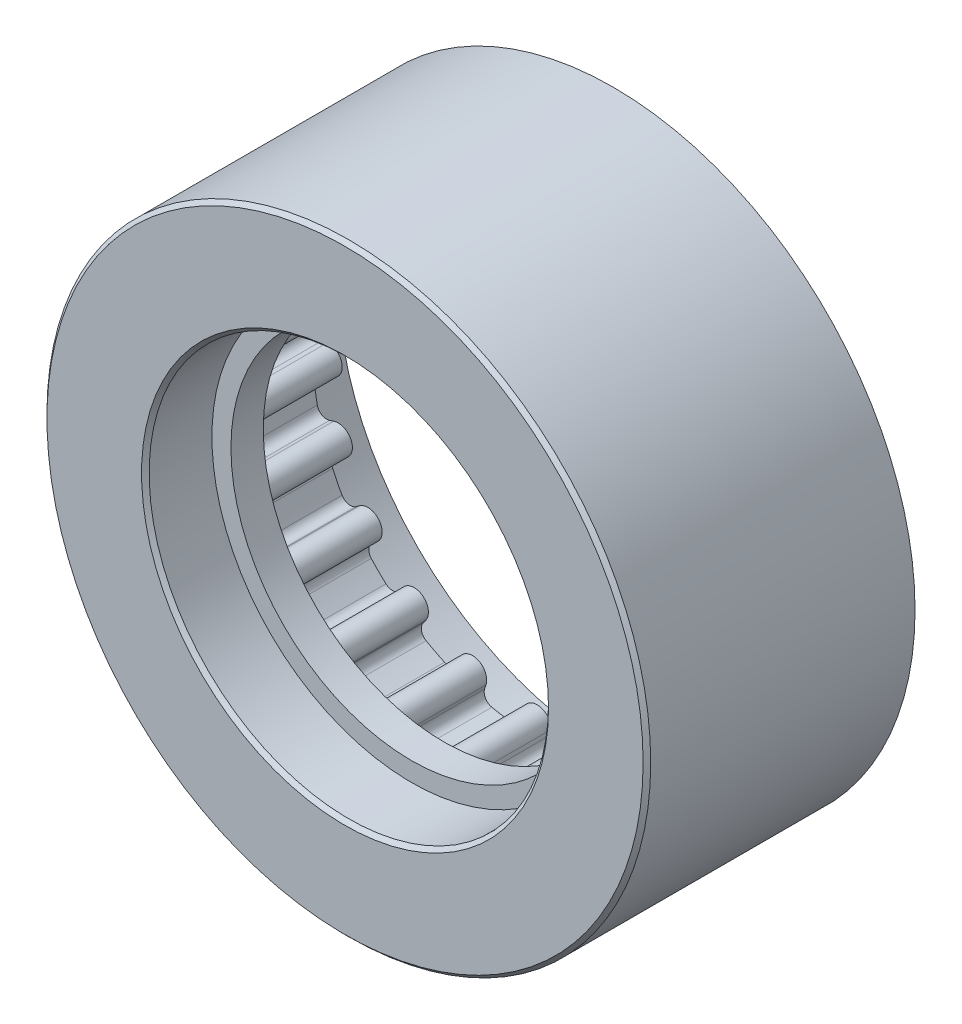
SolidWorks part; units mm, degrees
ref_plane "Ebene vorne" through (0, 0, 0) normal (0, 0, 1) x (1, 0, 0)
ref_plane "Ebene oben" through (0, 0, 0) normal (0, 1, 0) x (1, 0, 0)
ref_plane "Ebene rechts" through (0, 0, 0) normal (1, 0, 0) x (0, 0, -1)
ref_plane "Ebene1" through (0, 0, 0) normal (0, -1, 0) x (1, 0, 0)
sketch "Skizze1" plane through (0, 0, 0) normal (0, -1, 0) x (1, 0, 0)
  line L0 (31.75, 10.8) -> (0, 10.8)
  line L1 (0, 10.8) -> (0, -7)
  line L2 (0, -7) -> (31.75, -7)
  line L3 (31.75, -7) -> (31.75, 10.8)
  line L4 (0, 10.8) -> (0, -7) construction
revolve "Rotation1" add sketch "Skizze1" angle 360 about L4 reverse direction yes
sketch "Skizze2" plane through (0, 0, 10.8) normal (0, 0, 1) x (1, 0, 0)
  line L0 (-8.225, 20.4597) -> (-8.7046, 21.936)
  line L1 (-12.6302, 19.9359) -> (-11.7178, 18.6801)
  line L2 (-14.1448, 16.9167) -> (-15.0572, 18.1725)
  line L3 (-18.1725, 15.0572) -> (-16.9167, 14.1448)
  line L4 (-18.6801, 11.7178) -> (-19.9359, 12.6302)
  line L5 (-21.936, 8.7046) -> (-20.4597, 8.225)
  line L6 (-21.3868, 5.3718) -> (-22.8631, 5.8515)
  line L7 (-23.5523, 1.5) -> (-22, 1.5)
  line L8 (-22, -1.5) -> (-23.5523, -1.5)
  line L9 (-22.8631, -5.8515) -> (-21.3868, -5.3718)
  line L10 (-20.4597, -8.225) -> (-21.936, -8.7046)
  line L11 (-19.9359, -12.6302) -> (-18.6801, -11.7178)
  line L12 (-16.9167, -14.1448) -> (-18.1725, -15.0572)
  line L13 (-15.0572, -18.1725) -> (-14.1448, -16.9167)
  line L14 (-11.7178, -18.6801) -> (-12.6302, -19.9359)
  line L15 (-8.7046, -21.936) -> (-8.225, -20.4597)
  line L16 (-5.3718, -21.3868) -> (-5.8515, -22.8631)
  line L17 (-1.5, -23.5523) -> (-1.5, -22)
  line L18 (1.5, -22) -> (1.5, -23.5523)
  line L19 (5.8515, -22.8631) -> (5.3718, -21.3868)
  line L20 (8.225, -20.4597) -> (8.7046, -21.936)
  line L21 (12.6302, -19.9359) -> (11.7178, -18.6801)
  line L22 (14.1448, -16.9167) -> (15.0572, -18.1725)
  line L23 (18.1725, -15.0572) -> (16.9167, -14.1448)
  line L24 (18.6801, -11.7178) -> (19.9359, -12.6302)
  line L25 (21.936, -8.7046) -> (20.4597, -8.225)
  line L26 (21.3868, -5.3718) -> (22.8631, -5.8515)
  line L27 (23.5523, -1.5) -> (22, -1.5)
  line L28 (22, 1.5) -> (23.5523, 1.5)
  line L29 (22.8631, 5.8515) -> (21.3868, 5.3718)
  line L30 (20.4597, 8.225) -> (21.936, 8.7046)
  line L31 (19.9359, 12.6302) -> (18.6801, 11.7178)
  line L32 (16.9167, 14.1448) -> (18.1725, 15.0572)
  line L33 (15.0572, 18.1725) -> (14.1448, 16.9167)
  line L34 (11.7178, 18.6801) -> (12.6302, 19.9359)
  line L35 (8.7046, 21.936) -> (8.225, 20.4597)
  line L36 (5.3718, 21.3868) -> (5.8515, 22.8631)
  line L37 (1.5, 23.5523) -> (1.5, 22)
  line L38 (-1.5, 22) -> (-1.5, 23.5523)
  line L39 (-5.8515, 22.8631) -> (-5.3718, 21.3868)
  arc A0 (-8.7046, 21.936) -> (-12.6302, 19.9359) centre (0, 0) ccw
  arc A1 (-11.7178, 18.6801) -> (-14.1448, 16.9167) centre (-12.9313, 17.7984) cw
  arc A2 (-15.0572, 18.1725) -> (-18.1725, 15.0572) centre (0, 0) ccw
  arc A3 (-16.9167, 14.1448) -> (-18.6801, 11.7178) centre (-17.7984, 12.9313) cw
  arc A4 (-19.9359, 12.6302) -> (-21.936, 8.7046) centre (0, 0) ccw
  arc A5 (-20.4597, 8.225) -> (-21.3868, 5.3718) centre (-20.9232, 6.7984) cw
  arc A6 (-22.8631, 5.8515) -> (-23.5523, 1.5) centre (0, 0) ccw
  arc A7 (-22, 1.5) -> (-22, -1.5) centre (-22, 0) cw
  arc A8 (-23.5523, -1.5) -> (-22.8631, -5.8515) centre (0, 0) ccw
  arc A9 (-21.3868, -5.3718) -> (-20.4597, -8.225) centre (-20.9232, -6.7984) cw
  arc A10 (-21.936, -8.7046) -> (-19.9359, -12.6302) centre (0, 0) ccw
  arc A11 (-18.6801, -11.7178) -> (-16.9167, -14.1448) centre (-17.7984, -12.9313) cw
  arc A12 (-18.1725, -15.0572) -> (-15.0572, -18.1725) centre (0, 0) ccw
  arc A13 (-14.1448, -16.9167) -> (-11.7178, -18.6801) centre (-12.9313, -17.7984) cw
  arc A14 (-12.6302, -19.9359) -> (-8.7046, -21.936) centre (0, 0) ccw
  arc A15 (-8.225, -20.4597) -> (-5.3718, -21.3868) centre (-6.7984, -20.9232) cw
  arc A16 (-5.8515, -22.8631) -> (-1.5, -23.5523) centre (0, 0) ccw
  arc A17 (-1.5, -22) -> (1.5, -22) centre (0, -22) cw
  arc A18 (1.5, -23.5523) -> (5.8515, -22.8631) centre (0, 0) ccw
  arc A19 (5.3718, -21.3868) -> (8.225, -20.4597) centre (6.7984, -20.9232) cw
  arc A20 (8.7046, -21.936) -> (12.6302, -19.9359) centre (0, 0) ccw
  arc A21 (11.7178, -18.6801) -> (14.1448, -16.9167) centre (12.9313, -17.7984) cw
  arc A22 (15.0572, -18.1725) -> (18.1725, -15.0572) centre (0, 0) ccw
  arc A23 (16.9167, -14.1448) -> (18.6801, -11.7178) centre (17.7984, -12.9313) cw
  arc A24 (19.9359, -12.6302) -> (21.936, -8.7046) centre (0, 0) ccw
  arc A25 (20.4597, -8.225) -> (21.3868, -5.3718) centre (20.9232, -6.7984) cw
  arc A26 (22.8631, -5.8515) -> (23.5523, -1.5) centre (0, 0) ccw
  arc A27 (22, -1.5) -> (22, 1.5) centre (22, 0) cw
  arc A28 (23.5523, 1.5) -> (22.8631, 5.8515) centre (0, 0) ccw
  arc A29 (21.3868, 5.3718) -> (20.4597, 8.225) centre (20.9232, 6.7984) cw
  arc A30 (21.936, 8.7046) -> (19.9359, 12.6302) centre (0, 0) ccw
  arc A31 (18.6801, 11.7178) -> (16.9167, 14.1448) centre (17.7984, 12.9313) cw
  arc A32 (18.1725, 15.0572) -> (15.0572, 18.1725) centre (0, 0) ccw
  arc A33 (14.1448, 16.9167) -> (11.7178, 18.6801) centre (12.9313, 17.7984) cw
  arc A34 (12.6302, 19.9359) -> (8.7046, 21.936) centre (0, 0) ccw
  arc A35 (8.225, 20.4597) -> (5.3718, 21.3868) centre (6.7984, 20.9232) cw
  arc A36 (5.8515, 22.8631) -> (1.5, 23.5523) centre (0, 0) ccw
  arc A37 (1.5, 22) -> (-1.5, 22) centre (0, 22) cw
  arc A38 (-1.5, 23.5523) -> (-5.8515, 22.8631) centre (0, 0) ccw
  arc A39 (-5.3718, 21.3868) -> (-8.225, 20.4597) centre (-6.7984, 20.9232) cw
extrude "Schnitt-Linear austragen1" cut sketch "Skizze2" against normal through all
sketch "Skizze3" plane through (0, 0, 0) normal (0, 1, 0) x (1, 0, 0)
  line L0 (29, 7) -> (0, 7)
  line L1 (0, 7) -> (0, -1)
  line L2 (0, -1) -> (26, -1)
  line L3 (26, -1) -> (27, 0)
  line L4 (27, 0) -> (29, 0)
  line L5 (29, 0) -> (29, 7)
  line L6 (0, 7) -> (0, -1) construction
revolve "Schnitt-Rotation1" cut sketch "Skizze3" angle 360 about L6 reverse direction yes
fillet "Verrundung1" radius 1 40 edges at (22.8631, 5.8515, 5.9) (12.6302, -19.9359, 5.9) (1.5, 23.5523, 5.9) (-1.5, 23.5523, 5.9) (21.936, -8.7046, 5.9) (-8.7046, 21.936, 5.9) (15.0572, 18.1725, 5.9) (-12.6302, 19.9359, 5.9) (5.8515, -22.8631, 5.9) (-15.0572, 18.1725, 5.9) (18.1725, -15.0572, 5.9) (-18.1725, 15.0572, 5.9) (23.5523, -1.5, 5.9) (-19.9359, 12.6302, 5.9) (19.9359, 12.6302, 5.9) (-21.936, 8.7046, 5.9) (8.7046, 21.936, 5.9) (-22.8631, 5.8515, 5.9) (1.5, -23.5523, 5.9) (-23.5523, 1.5, 5.9) (8.7046, -21.936, 5.9) (-23.5523, -1.5, 5.9) (15.0572, -18.1725, 5.9) (-22.8631, -5.8515, 5.9) (19.9359, -12.6302, 5.9) (-21.936, -8.7046, 5.9) (22.8631, -5.8515, 5.9) (-19.9359, -12.6302, 5.9) (23.5523, 1.5, 5.9) (-18.1725, -15.0572, 5.9) (21.936, 8.7046, 5.9) (-15.0572, -18.1725, 5.9) (18.1725, 15.0572, 5.9) (-12.6302, -19.9359, 5.9) (12.6302, 19.9359, 5.9) (-8.7046, -21.936, 5.9) (5.8515, 22.8631, 5.9) (-5.8515, -22.8631, 5.9) (-1.5, -23.5523, 5.9) (-5.8515, 22.8631, 5.9) tangent propagation no
sketch "Skizze13" plane through (0, 0, 10.8) normal (0, 0, 1) x (1, 0, 0)
  circle A1 centre (0, 0) radius 31.75
  circle A162 centre (0, 0) radius 21
  dimension "D1" = 42
extrude "Aufsatz-Linear austragen1" add sketch "Skizze13" along normal blind 10.4
sketch "Skizze14" plane through (0, 0, 10.8) normal (0, 0, -1) x (-1, 0, 0)
  circle A0 centre (0, 0) radius 19
  circle A1 centre (0, 0) radius 21
  arc M3 (20.9716, -1.092) -> (20.2826, -5.4421) centre (0, 0) cw
  dimension "D1" = 38
extrude "Aufsatz-Linear austragen2" add sketch "Skizze14" against normal offset from surface (3.4 mm away) 7 contours A1 A0 M3 region at (-20.3991, -0.5307, 10.8) up to face at (31.75, 0, 21.2)
chamfer "Fase5" distance 0.4 angle 45 2 edges at (21, 0, 21.2) (31.75, 0, 21.2)
